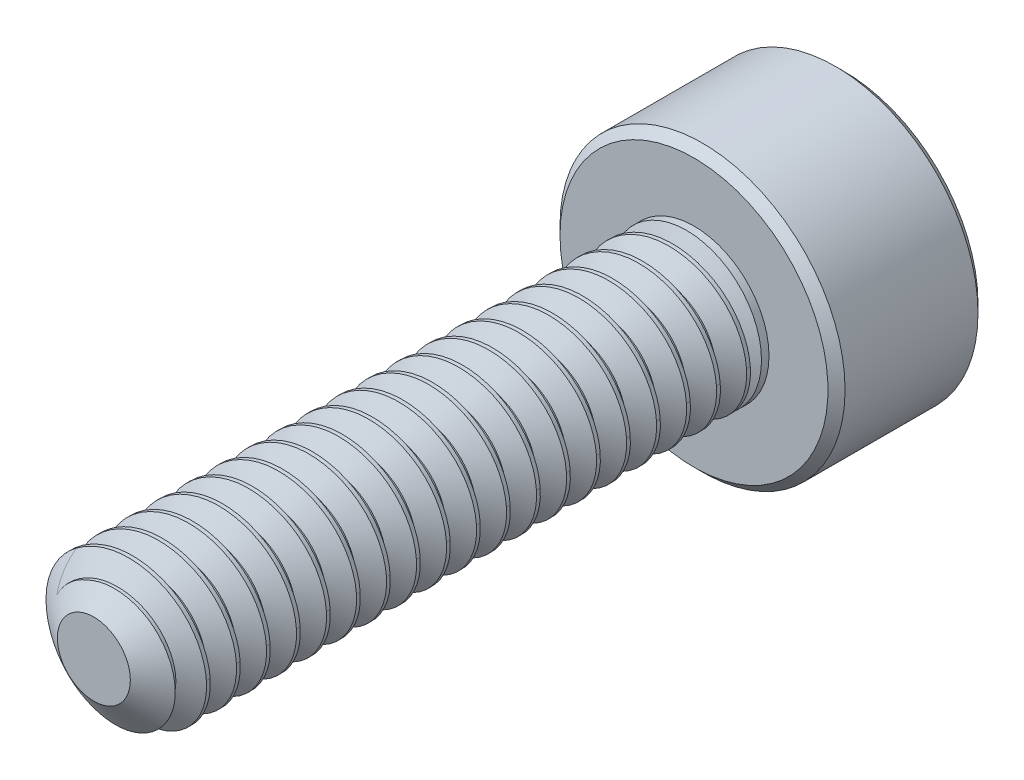
SolidWorks part; units mm, degrees
ref_plane "Front Plane" through (0, 0, 0) normal (0, 0, 1) x (1, 0, 0)
ref_plane "Top Plane" through (0, 0, 0) normal (0, 1, 0) x (1, 0, 0)
ref_plane "Right Plane" through (0, 0, 0) normal (1, 0, 0) x (0, 0, -1)
sketch "Sketch1" plane through (0, 0, 0) normal (0, 0, 1) x (1, 0, 0)
  circle A0 centre (0, 0) radius 1
  dimension "OD" = 2
extrude "Extrude1" add sketch "Sketch1" against normal blind 8
sketch "Sketch2" plane through (0, 0, 0) normal (0, 0, 1) x (1, 0, 0)
  circle A0 centre (0, 0) radius 1 construction
  circle A1 centre (0, 0) radius 1
curve "Helix/Spiral1" pitch 0.4 height 8.4 radius 1 centre (0, 0, 0) axis (0, 0, -1) start towards (0, 1, 0) parameters "pitch"=0.4
sketch "Sketch3" plane through (0, 0, 0) normal (1, 0, 0) x (0, 0, -1)
  line L0 (-0.35, 1) -> (-0.2, 0.7402)
  line L1 (-0.2, 0.7402) -> (-0.15, 0.7402)
  line L2 (-0.15, 0.7402) -> (0, 1)
  line L3 (-0.35, 1) -> (0, 1)
  line L4 (-0.175, 1) -> (-0.175, 0.7402) construction
  line L5 (-0.275, 0.8701) -> (-0.075, 0.8701) construction
  line L6 (0, 1) -> (0, -1) construction
  line L7 (0, -1) -> (8, -1) construction
  point P11 (1.8, -1)
  dimension "D1" = 0.05
  dimension "D2" = 0.2
  dimension "D3" = 60
  dimension "D4" = 1.8
sweep "Cut-Sweep1" cut profiles "Sketch3" path "Helix/Spiral1"
sketch "Sketch4" plane through (0, 0, 0) normal (1, 0, 0) x (0, 0, -1)
  line L0 (0.3598, 1) -> (0, 0.4862)
  line L1 (0, 0.4862) -> (0, 1)
  line L2 (0.3598, 1) -> (0, 1)
  line L3 (-0.35, 1) -> (0, 1) construction
  line L4 (0, 0) -> (7.0209, 0) construction
  dimension "D1" = 55
  dimension "D2" = 0.254
revolve "Cut-Revolve1" cut sketch "Sketch4" angle 360 about L4
sketch "Sketch5" plane through (0, 0, 0) normal (1, 0, 0) x (0, 0, -1)
  line L0 (8, -0.7473) -> (8, 0.7135) construction
  line L1 (8, 1) -> (0.1203, 1)
  line L2 (8, 1) -> (8, 0)
  line L3 (8, 0) -> (0.0001, 0)
  line L4 (0.0001, 0.6698) -> (0.0001, 0)
  line L5 (0.1203, 1) -> (0.0001, 0.6698)
  line L6 (0, 0) -> (9.9695, 0) construction
  point P3 (0.0001, 1)
  point P10 (0.0001, 1)
  dimension "D1" = 0.3302
  dimension "Thread min" = 0.0001
  dimension "D3" = 20
revolve "partially thread" [suppressed] add sketch "Sketch5" angle 360 about L6
sketch "Sketch6" plane through (0, 0, -8) normal (0, 0, -1) x (-1, 0, 0)
  circle A0 centre (0, 0) radius 1.9
  dimension "head dia" = 3.8
extrude "Extrude2" add sketch "Sketch6" along normal blind 2
sketch "Sketch7" plane through (0, 0, -10) normal (0, 0, -1) x (-1, 0, 0)
  line L1 (0, 0.866) -> (-0.75, 0.433)
  line L2 (-0.75, 0.433) -> (-0.75, -0.433)
  line L3 (-0.75, -0.433) -> (0, -0.866)
  line L4 (0, -0.866) -> (0.75, -0.433)
  line L5 (0.75, -0.433) -> (0.75, 0.433)
  line L6 (0.75, 0.433) -> (0, 0.866)
  circle A0 centre (0, 0) radius 0.75 construction
  dimension "hex dia" = 1.5
extrude "Cut-Extrude1" cut sketch "Sketch7" against normal blind 1.125
sketch "Sketch8" plane through (0, 0, -10) normal (0, 0, -1) x (-1, 0, 0)
  circle A0 centre (0, 0) radius 0.866
extrude "Cut-Extrude2" cut sketch "Sketch8" against normal through all draft 45
chamfer "Chamfer1" distance 0.114 angle 45 2 edges at (-1.9, 0, -10) (-1.9, 0, -8)
sketch "Sketch9" plane through (0, 0, 0) normal (1, 0, 0) x (0, 0, -1)
  line L0 (0, 1) -> (0, -1) construction
  line L1 (2.2, 1) -> (2.2, -1) construction
  dimension "D1" = 2.2
sketch "Sketch10" plane through (0, 0, 0) normal (1, 0, 0) x (0, 0, -1)
  line L0 (8, 1) -> (8, 0)
  line L1 (8, 1) -> (7.9, 1)
  line L2 (7.9, 1) -> (7.4858, 0)
  line L3 (8, 0) -> (7.4858, 0)
  line L4 (8, 1.786) -> (8, -1.786) construction
  dimension "D1" = 22.5
  dimension "D2" = 0.1
revolve "Revolve1" add sketch "Sketch10" angle 360 about L3
equation "\"D3@Helix/Spiral1\" = \"screw length@Extrude1\"+\"pitch@Helix/Spiral1\""
equation "\"D1@Sketch3\" = \"pitch@Helix/Spiral1\"*.125"
equation "\"D2@Sketch3\" = \"pitch@Helix/Spiral1\"*.5"
equation "\"D1@Cut-Extrude1\" = \"hex dia@Sketch7\"*.75"
equation "\"D1@Chamfer1\" = \"head dia@Sketch6\"*.03"
equation "\"D1@Sketch9\" = \"pitch@Helix/Spiral1\"*5.5"
equation "\"D2@Sketch10\" = \"pitch@Helix/Spiral1\"*.25"
equation "\"D4@Sketch3\" = \"pitch@Helix/Spiral1\"*4.50"
